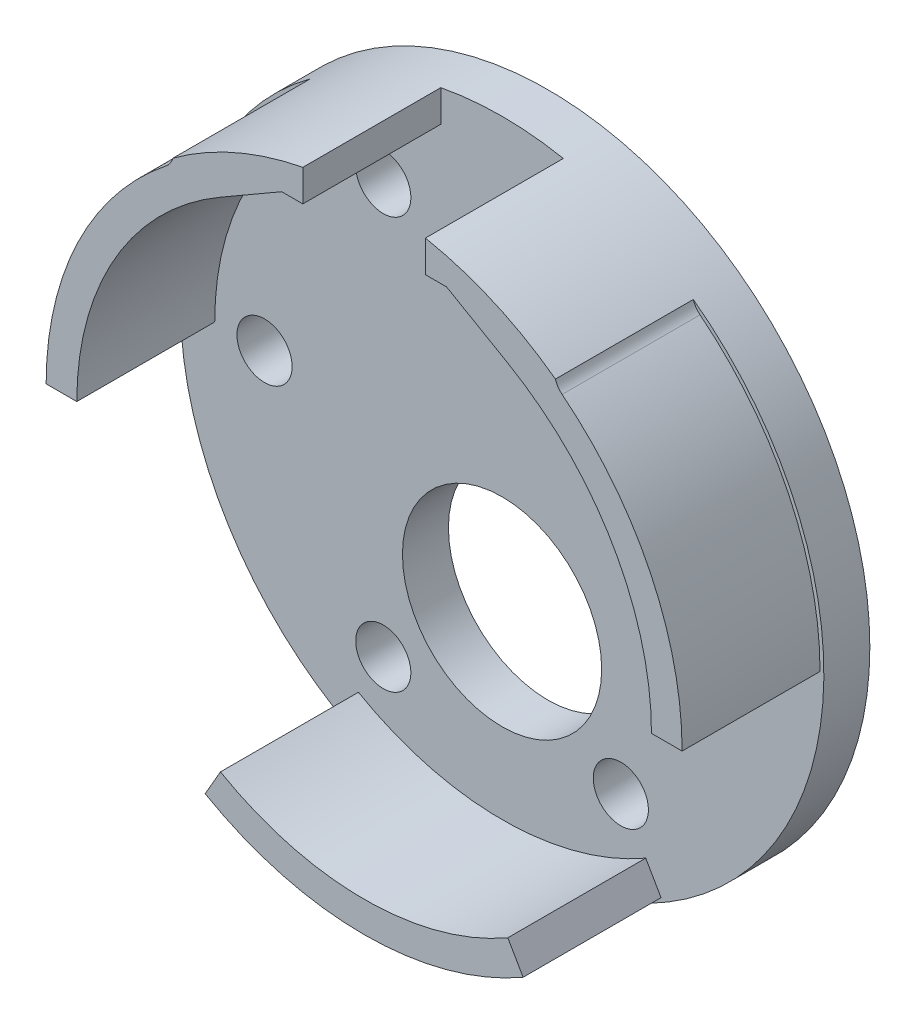
SolidWorks part; units mm, degrees
ref_plane "Front Plane" through (0, 0, 0) normal (0, 0, 1) x (1, 0, 0)
ref_plane "Top Plane" through (0, 0, 0) normal (0, 1, 0) x (1, 0, 0)
ref_plane "Right Plane" through (0, 0, 0) normal (1, 0, 0) x (0, 0, -1)
sketch "Sketch1" plane through (0, 0, 0) normal (0, 0, 1) x (1, 0, 0)
  line L0 (0, 25) -> (0, 0) construction
  line L1 (0, 1.4545) -> (-18.5, 1.4545) construction
  line L2 (-7.75, 14.8779) -> (0, 1.4545) construction
  line L3 (-7.75, -11.9689) -> (0, 1.4545) construction
  line L4 (-45, 0) -> (0, 0) construction
  line L5 (-46.6249, -4.7286) -> (-6.8247, -18.4056) construction
  line L6 (-48.4169, 3.6504) -> (-11.959, 37.7762)
  line L7 (46.6249, -4.7286) -> (6.8247, -18.4056) construction
  line L8 (48.4169, 3.6504) -> (11.959, 37.7762)
  line L9 (-16, -19.5455) -> (16, -19.5455)
  line L10 (-17.6678, -19.1542) -> (-47.2237, -4.4783)
  line L11 (17.6678, -19.1542) -> (47.2237, -4.4783)
  circle A0 centre (-25, 0) radius 2.5
  circle A1 centre (0, 1.4545) radius 18.5 construction
  circle A2 centre (0, -5.5455) radius 6.5
  circle A3 centre (0, 1.4545) radius 15.5 construction
  circle A4 centre (-7.75, 14.8779) radius 1.8
  circle A5 centre (-15.5, 1.4545) radius 1.8
  circle A6 centre (-7.75, -11.9689) radius 1.8
  circle A7 centre (-45, 0) radius 5 construction
  circle A8 centre (0, 25) radius 17.5 construction
  circle A9 centre (0, 1.4545) radius 21 construction
  arc A10 (-48.4169, 3.6504) -> (-46.6249, -4.7286) centre (-45, 0) ccw construction
  circle A11 centre (7.75, -11.9689) radius 1.8
  circle A12 centre (7.75, 14.8779) radius 1.8
  circle A13 centre (15.5, 1.4545) radius 1.8
  circle A14 centre (25, 0) radius 2.5
  arc A15 (48.4169, 3.6504) -> (46.6249, -4.7286) centre (45, 0) cw construction
  arc A16 (-11.959, 37.7762) -> (11.959, 37.7762) centre (0, 25) cw
  arc A17 (6.8247, -18.4056) -> (-6.8247, -18.4056) centre (0, 1.4545) cw construction
  circle A18 centre (-45, 0) radius 2.5
  circle A19 centre (45, 0) radius 2.5
  circle A20 centre (-16, -15.7955) radius 3.75 construction
  circle A21 centre (-16, -15.7955) radius 2.5
  arc A22 (-48.4169, 3.6504) -> (-47.2237, -4.4783) centre (-45, 0) ccw
  arc A23 (-17.6678, -19.1542) -> (-16, -19.5455) centre (-16, -15.7955) ccw
  circle A24 centre (16, -15.7955) radius 3.75 construction
  circle A25 centre (16, -15.7955) radius 2.5
  arc A26 (17.6678, -19.1542) -> (16, -19.5455) centre (16, -15.7955) cw
  arc A27 (48.4169, 3.6504) -> (47.2237, -4.4783) centre (45, 0) cw
  point P53 (0, -19.5455)
  dimension "D1" = 5
  dimension "D2" = 50
  dimension "D3" = 37
  dimension "D5" = 13
  dimension "D9" = 3.6
  dimension "D10" = 31
  dimension "D12" = 10
  dimension "D13" = 35
  dimension "D15" = 42
  dimension "D16" = 5
  dimension "D17" = 7.5
  dimension "D18" = 5
  dimension "D4" = 1.4545
  dimension "D6" = 7
  dimension "D7" = 60
  dimension "D8" = 60
  dimension "D11" = 45
  dimension "D14" = 25
  dimension "D19" = 16
extrude "Boss-Extrude1" add sketch "Sketch1" along normal blind 3
sketch "Sketch2" plane through (0, 0, 3) normal (0, 0, 1) x (1, 0, 0)
  line L0 (0, 0) -> (0, 22.2045) construction
  line L1 (0, 1.4545) -> (-10.375, -16.5155) construction
  line L2 (0, 1.4545) -> (10.375, -16.5155) construction
  line L3 (0, 1.4545) -> (-20.75, 1.4545) construction
  line L4 (0, 1.4545) -> (-10.375, 19.4245) construction
  line L5 (-10.375, 19.4245) -> (-9.375, 17.6925)
  line L6 (-20.75, 1.4545) -> (-18.75, 1.4545)
  line L7 (-10.375, -16.5155) -> (-9.375, -14.7835)
  line L8 (10.375, -16.5155) -> (9.375, -14.7835)
  line L9 (10.375, 19.4245) -> (9.375, 17.6925)
  line L10 (20.75, 1.4545) -> (18.75, 1.4545)
  circle A0 centre (0, 1.4545) radius 18.5 construction
  circle A1 centre (0, 1.4545) radius 18.5 construction
  circle A2 centre (0, 1.4545) radius 18.75 construction
  circle A3 centre (0, 1.4545) radius 20.75 construction
  arc A4 (-20.75, 1.4545) -> (-10.375, 19.4245) centre (0, 1.4545) cw
  arc A5 (-18.75, 1.4545) -> (-9.375, 17.6925) centre (0, 1.4545) cw
  arc A6 (-9.375, -14.7835) -> (9.375, -14.7835) centre (0, 1.4545) ccw
  arc A7 (-10.375, -16.5155) -> (10.375, -16.5155) centre (0, 1.4545) ccw
  arc A8 (20.75, 1.4545) -> (10.375, 19.4245) centre (0, 1.4545) ccw
  arc A9 (18.75, 1.4545) -> (9.375, 17.6925) centre (0, 1.4545) ccw
  dimension "D1" = 37.5
  dimension "D2" = 2
  dimension "D3" = 150
  dimension "D4" = 150
  dimension "D5" = 60
  dimension "D6" = 60
extrude "Boss-Extrude2" add sketch "Sketch2" along normal blind 39 contours L6 A5 L5 A4 | L7 A7 L8 A6 | A9 L10 A8 L9 region at (-16.3471, 10.8925, 3) region at (0, -17.4215, 3) region at (16.3471, 10.8925, 3)
sketch "Sketch3" plane through (0, 0, 3) normal (0, 0, 1) x (1, 0, 0)
  line L0 (0, 0) -> (0, 23) construction
  line L1 (-12.5, 38) -> (12.5, 38) construction
  line L2 (-12.5, 38) -> (-12.5, 23) construction
  line L3 (-12.5, 23) -> (12.5, 23) construction
  line L4 (12.5, 38) -> (12.5, 23) construction
  line L5 (0, 25) -> (0, 0) construction
  line L6 (-17.5, 29) -> (-17.5, 23)
  line L7 (-17.5, 23) -> (-4, 23)
  line L8 (-4, 23) -> (-4, 20)
  line L9 (-4, 20) -> (-5.3783, 20)
  line L10 (-17.5, 29) -> (-20.5, 29)
  line L11 (-20.5, 29) -> (-20.5, 20)
  line L12 (-20.5, 20) -> (-13.7246, 20)
  line L13 (-9.375, 17.6925) -> (-5.3783, 20)
  line L14 (-12.9186, 17.6925) -> (-9.375, 17.6925)
  arc A0 (-9.375, 17.6925) -> (-18.75, 1.4545) centre (0, 1.4545) ccw construction
  arc A1 (-13.7246, 20) -> (-12.9186, 17.6925) centre (-13.7246, 18.7055) cw
  arc A2 (-10.375, 19.4245) -> (-20.75, 1.4545) centre (0, 1.4545) ccw construction
  dimension "D1" = 25
  dimension "D2" = 15
  dimension "D3" = 23
  dimension "D4" = 8
  dimension "D5" = 3
  dimension "D6" = 35
  dimension "D7" = 3
  dimension "D8" = 6
extrude "Boss-Extrude3" add sketch "Sketch3" along normal up to surface (39 mm away) up to face at (-15.9583, 10.668, 42)
mirror "Mirror1" about plane through (0, 0, 0) normal (1, 0, 0) of "Boss-Extrude3"
sketch "Sketch4" plane through (0, 23, 0) normal (0, 1, 0) x (1, 0, 0)
  line L0 (-13.7246, -42) -> (-13.7246, -3) construction
  line L1 (-13.7246, -42) -> (-13.7246, -3) construction
  line L2 (-15.7246, -17.5) -> (-15.7246, -27.5) construction
  line L3 (-14.2246, -17.5) -> (-14.2246, -27.5)
  line L4 (-17.2246, -17.5) -> (-17.2246, -27.5)
  line L5 (-15.7246, -22.5) -> (-13.7246, -22.5) construction
  line L6 (0, 0) -> (0, -40.251) construction
  line L7 (15.7246, -17.5) -> (15.7246, -27.5) construction
  line L8 (14.2246, -17.5) -> (14.2246, -27.5)
  line L9 (17.2246, -17.5) -> (17.2246, -27.5)
  arc A0 (-14.2246, -17.5) -> (-17.2246, -17.5) centre (-15.7246, -17.5) ccw
  arc A1 (-17.2246, -27.5) -> (-14.2246, -27.5) centre (-15.7246, -27.5) ccw
  arc A2 (14.2246, -17.5) -> (17.2246, -17.5) centre (15.7246, -17.5) cw
  arc A3 (17.2246, -27.5) -> (14.2246, -27.5) centre (15.7246, -27.5) cw
  point P4 (-15.7246, -22.5)
  point P16 (15.7246, -22.5)
  dimension "D1" = 3
  dimension "D2" = 2
  dimension "D3" = 10
extrude "Cut-Extrude1" cut sketch "Sketch4" against normal up to surface (3 mm away) up to face at (-17.1123, 20, 22.5)
sketch "Sketch5" plane through (0, 0, 3) normal (0, 0, 1) x (1, 0, 0)
  line L0 (-43.7844, 23.3468) -> (-43.7844, 6.0404)
  line L1 (-43.7844, 6.0404) -> (-29.1766, -7.7395)
  line L2 (-27.9848, -4.7395) -> (-40.7844, 7.3346)
  line L3 (-40.7844, 7.3346) -> (-40.7844, 23.3468)
  line L4 (-43.7844, 23.3468) -> (-40.7844, 23.3468)
  line L6 (-27.9848, -4.7395) -> (-18.0861, -4.7395)
  line L7 (-29.1766, -7.7395) -> (-18.0861, -7.7395)
  line L8 (-18.0861, -7.7395) -> (-18.0861, -4.7395)
  dimension "D1" = 3
  dimension "D2" = 3
  dimension "D3" = 3
extrude "Boss-Extrude4" add sketch "Sketch5" along normal blind 34
mirror "Mirror2" about plane through (0, 0, 0) normal (1, 0, 0) of "Boss-Extrude4"
sketch "Sketch6" plane through (0, 0, 3) normal (0, 0, -1) x (-1, 0, 0)
  line L4 (40.7844, 23.3468) -> (40.7844, 10.7946)
  line L5 (40.7844, 10.7946) -> (43.7844, 7.9865)
  line L6 (43.7844, 7.9865) -> (43.7844, 23.3468)
  line L7 (43.7844, 23.3468) -> (40.7844, 23.3468)
  line L8 (40.7844, 23.3468) -> (40.7844, 10.7946)
  line L9 (40.7844, 10.7946) -> (43.7844, 7.9865)
  line L10 (43.7844, 7.9865) -> (43.7844, 23.3468)
  line L11 (43.7844, 23.3468) -> (40.7844, 23.3468)
  line L12 (-43.7844, 23.3468) -> (-43.7844, 7.9865)
  line L13 (-43.7844, 7.9865) -> (-40.7844, 10.7946)
  line L14 (-40.7844, 10.7946) -> (-40.7844, 23.3468)
  line L15 (-40.7844, 23.3468) -> (-43.7844, 23.3468)
  line L16 (-43.7844, 23.3468) -> (-43.7844, 7.9865)
  line L17 (-43.7844, 7.9865) -> (-40.7844, 10.7946)
  line L18 (-40.7844, 10.7946) -> (-40.7844, 23.3468)
  line L19 (-40.7844, 23.3468) -> (-43.7844, 23.3468)
  dimension "D1" = 0
  dimension "D2" = 0
extrude "Boss-Extrude5" add sketch "Sketch6" along normal up to surface (3 mm away) up to face at (0, 0.0404, 0)
sketch "Sketch7" plane through (0, 0, 3) normal (0, 0, 1) x (1, 0, 0)
  circle A0 centre (-18.7282, -11.5671) radius 3.75 construction
  circle A1 centre (-18.7282, -11.5671) radius 2.5
  dimension "D1" = 7.5
  dimension "D2" = 5
sketch "Sketch8" plane through (0, 0, 3) normal (0, 0, 1) x (1, 0, 0)
  line L1 (-51.7865, 53.5853) -> (50.6856, 53.5853)
  line L2 (-51.7865, 53.5853) -> (-51.7865, -24.7012)
  line L3 (-51.7865, -24.7012) -> (50.6856, -24.7012)
  line L4 (50.6856, 53.5853) -> (50.6856, -24.7012)
  line L5 (50.6856, -1.9689) -> (-24.865, -1.9689)
  line L6 (50.6856, -1.9689) -> (50.6856, -10.9708)
  line L7 (50.6856, -10.9708) -> (-24.865, -10.9708)
  line L8 (-24.865, -1.9689) -> (-24.865, -10.9708)
  circle A0 centre (0, 1.4545) radius 21 construction
  circle A1 centre (0, 1.4545) radius 21
extrude "Cut-Extrude3" cut sketch "Sketch8" along normal through all contours A1 L7 L8 L5 L4 L1 L2 L3 | L5 A1 L7 | A1 L5 L8 L7 | A1 L7 L4 L5 region at (-0.5504, 52.2957, 3) region at (34.9447, -6.559, 3) region at (0, -6.324, 3) region at (-21.9468, -6.9687, 3)
sketch "Sketch9" plane through (0, 0, 3) normal (0, 0, 1) x (1, 0, 0)
  line L1 (-60.1211, 49.2614) -> (55.6206, 49.2614)
  line L2 (-60.1211, 49.2614) -> (-60.1211, -27.4703)
  line L3 (-60.1211, -27.4703) -> (55.6206, -27.4703)
  line L4 (55.6206, 49.2614) -> (55.6206, -27.4703)
  circle A0 centre (0, 1.4545) radius 21 construction
  circle A1 centre (0, 1.4545) radius 21
extrude "Cut-Extrude4" cut sketch "Sketch9" against normal blind 10
sketch "Sketch10" plane through (0, 0, 42) normal (0, 0, 1) x (1, 0, 0)
  line L1 (-27.9699, 25.8015) -> (24.4945, 25.8015)
  line L2 (-27.9699, 25.8015) -> (-27.9699, -25.8634)
  line L3 (-27.9699, -25.8634) -> (24.4945, -25.8634)
  line L4 (24.4945, 25.8015) -> (24.4945, -25.8634)
extrude "Cut-Extrude5" cut sketch "Sketch10" against normal blind 30
equation "\"D4@Sketch2\"=\"D3@Sketch2\""
